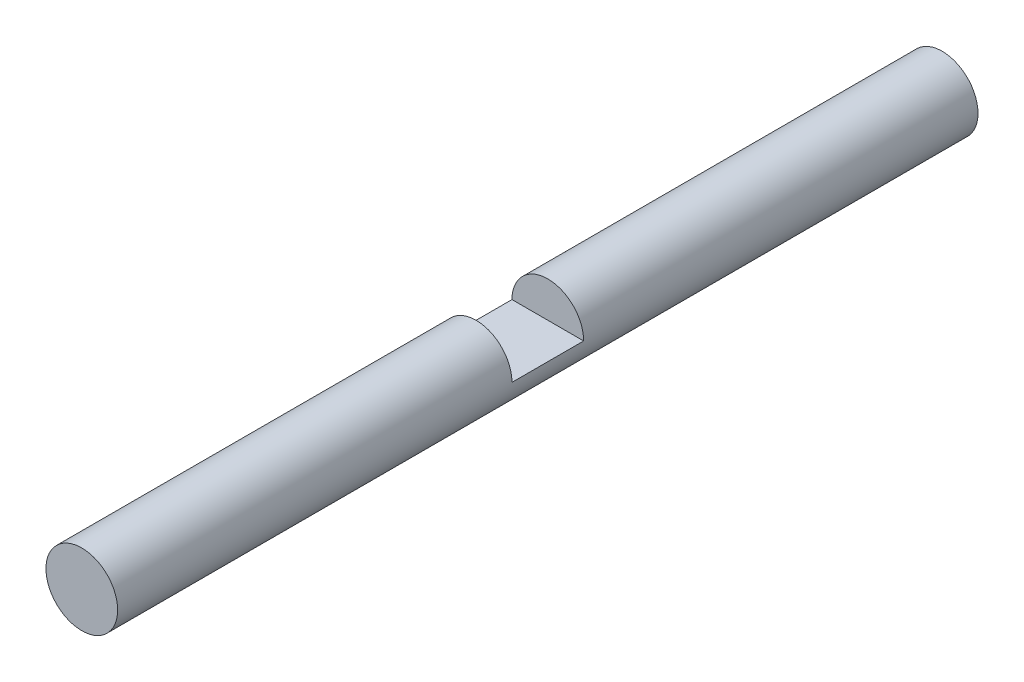
SolidWorks part; units mm, degrees
ref_plane "Front Plane" through (0, 0, 0) normal (0, 0, 1) x (1, 0, 0)
ref_plane "Top Plane" through (0, 0, 0) normal (0, 1, 0) x (1, 0, 0)
ref_plane "Right Plane" through (0, 0, 0) normal (1, 0, 0) x (0, 0, -1)
ref_axis "Axis1" through (0, 55, 0) along (0, -1, 0)
sketch "Sketch1" plane through (0, 0, 0) normal (0, 0, 1) x (1, 0, 0)
  circle A0 centre (0, 0) radius 2.5
  dimension "D1" = 5
extrude "Boss-Extrude1" add sketch "Sketch1" along normal blind 30 and the other way blind 30 contours A0
sketch "Sketch5" plane through (0, 0, 0) normal (0, 1, 0) x (1, 0, 0)
  line L1 (-2.5, -2.5) -> (2.5, -2.5)
  line L2 (-2.5, -2.5) -> (-2.5, 2.5)
  line L3 (-2.5, 2.5) -> (2.5, 2.5)
  line L4 (2.5, -2.5) -> (2.5, 2.5)
  line L5 (-2.5, -2.5) -> (2.5, 2.5) construction
  line L6 (-2.5, 2.5) -> (2.5, -2.5) construction
  point P0 (0, 0)
  dimension "D1" = 5
  dimension "D2" = 5
extrude "Cut-Extrude1" cut sketch "Sketch5" along normal blind 10
